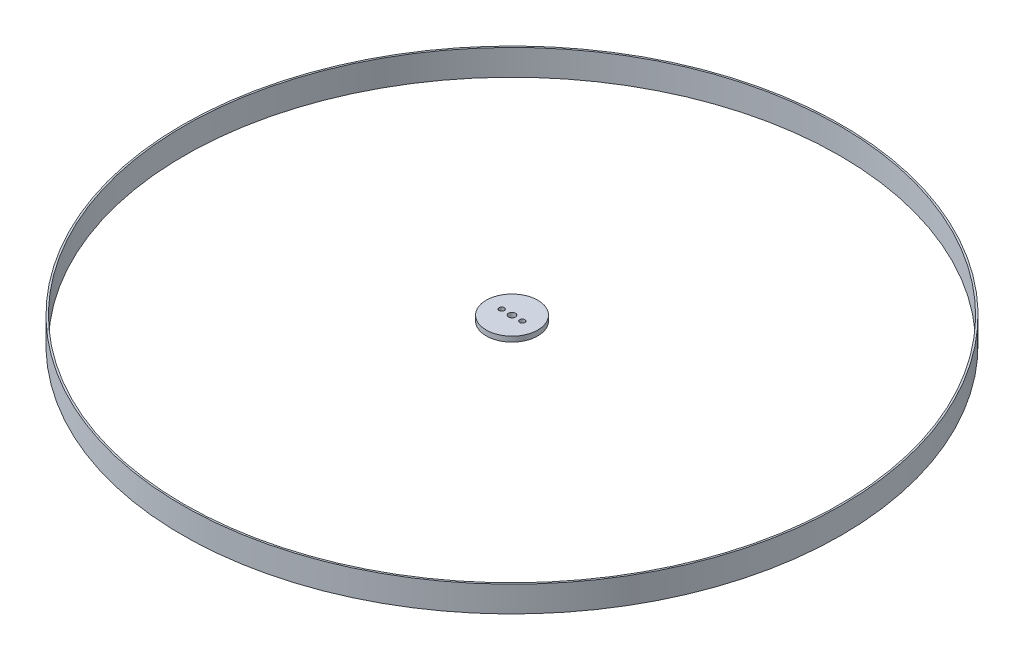
SolidWorks part; units mm, degrees
ref_plane "Front Plane" through (0, 0, 0) normal (0, 0, 1) x (1, 0, 0)
ref_plane "Top Plane" through (0, 0, 0) normal (0, 1, 0) x (1, 0, 0)
ref_plane "Right Plane" through (0, 0, 0) normal (1, 0, 0) x (0, 0, -1)
sketch "Sketch1" plane through (0, 0, 0) normal (0, 1, 0) x (1, 0, 0)
  circle A0 centre (0, 0) radius 2
  circle A2 centre (6, 0) radius 1.5
  circle A3 centre (-6, 0) radius 1.5
  circle A5 centre (0, 0) radius 15
  point P11 (0, 0)
  dimension "D1" = 2
extrude "Boss-Extrude1" add sketch "Sketch1" along normal blind 3 contours A5 A3 A2 A0 region at (-14.5757, 0, 0)
sketch "Sketch3" plane through (0, 3, 0) normal (0, 1, 0) x (1, 0, 0)
  circle A0 centre (0, 0) radius 190.5
extrude "Extrude-Thin3" add sketch "Sketch3" against normal blind 15 separate body thin thin type one direction wall 1
